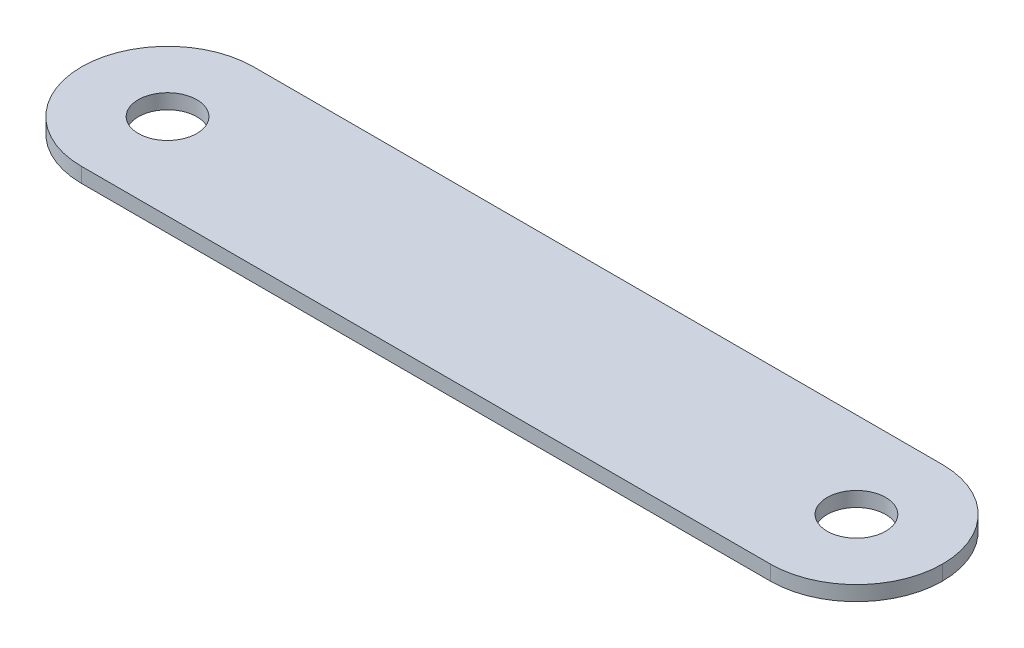
SolidWorks part; units mm, degrees
ref_plane "Front Plane" through (0, 0, 0) normal (0, 0, 1) x (1, 0, 0)
ref_plane "Top Plane" through (0, 0, 0) normal (0, 1, 0) x (1, 0, 0)
ref_plane "Right Plane" through (0, 0, 0) normal (1, 0, 0) x (0, 0, -1)
sketch "Sketch1" plane through (0, 0, 0) normal (0, 1, 0) x (1, 0, 0)
  line L1 (25, -5) -> (-25, -5)
  line L2 (25, -5) -> (25, 5)
  line L3 (25, 5) -> (-25, 5)
  line L4 (-25, -5) -> (-25, 5)
  line L5 (25, -5) -> (-25, 5) construction
  line L6 (25, 5) -> (-25, -5) construction
  point P0 (0, 0)
  dimension "D1" = 50
  dimension "D2" = 10
base flange "Base-Flange1" sketch "Sketch1" thickness 0.86 reverse thickness direction no parameters "D1"=0.7366
hole_wizard "M3 Clearance Hole1" positions "Sketch7" profile "Sketch6" hole size "M3" standard "ANSI Metric"
sketch "Sketch7" plane through (0, 0, 0) normal (0, 1, 0) x (1, 0, 0)
  line L0 (-25, 5) -> (-25, -5) construction
  line L1 (25, -5) -> (25, 5) construction
  point P0 (-20, 0)
  point P2 (20, 0)
  dimension "D1" = 5
  dimension "D2" = 5
sketch "Sketch6" plane through (-20, 0, 0) normal (1, 0, 0) x (0, 0, 1)
  line L0 (0, 0) -> (0, 2.3115)
  line L1 (0, 2.3115) -> (1.7, 1.29)
  line L2 (1.7, 1.29) -> (1.7, 0)
  line L5 (1.7, 0) -> (0, 0)
  line L10 (0, 2.3115) -> (-1.7, 1.29) construction
  line L11 (0, -6.35) -> (0, 107.95) construction
  dimension "Hole Dia." = 3.4
  dimension "Hole Depth" = 1.29
  dimension "Drill Angle" = 118
fillet "Fillet1" radius 5 4 edges at (25, -0.43, 5) (25, -0.43, -5) (-25, -0.43, -5) (-25, -0.43, 5)
sketch "Bend-Lines1" [suppressed] plane through (0, 0, 0) normal (0, 1, 0) x (1, 0, 0)
sketch "Bounding-Box1" [suppressed] plane through (0, 0, 0) normal (0, 1, 0) x (1, 0, 0)
sheet metal parameters "Sheet-Metal(1)" thickness 0.86 parameters "D1"=0.7366
flat pattern "Flat-Pattern(1)" [suppressed]
sketch "Bend-Lines2" plane through (0, 0, 0) normal (0, 1, 0) x (1, 0, 0)
sketch "Bounding-Box2" [suppressed] plane through (0, 0, 0) normal (0, 1, 0) x (1, 0, 0)
sheet metal parameters "Sheet-Metal(2)" thickness 0.86 parameters "D1"=0.7366
flat pattern "Flat-Pattern(1)"
sketch "Bend-Lines2" plane through (0, 0, 0) normal (0, 1, 0) x (1, 0, 0)
sketch3d "Bounding-Box2" [suppressed]
  line L0 (24.9998, -5, 0) -> (-24.9998, -5, 0) construction
  line L1 (24.9998, 5, 0) -> (-24.9998, 5, 0) construction
  line L2 (24.9998, -5, 0) -> (24.9998, 5, 0) construction
  line L3 (-24.9998, -5, 0) -> (-24.9998, 5, 0) construction
